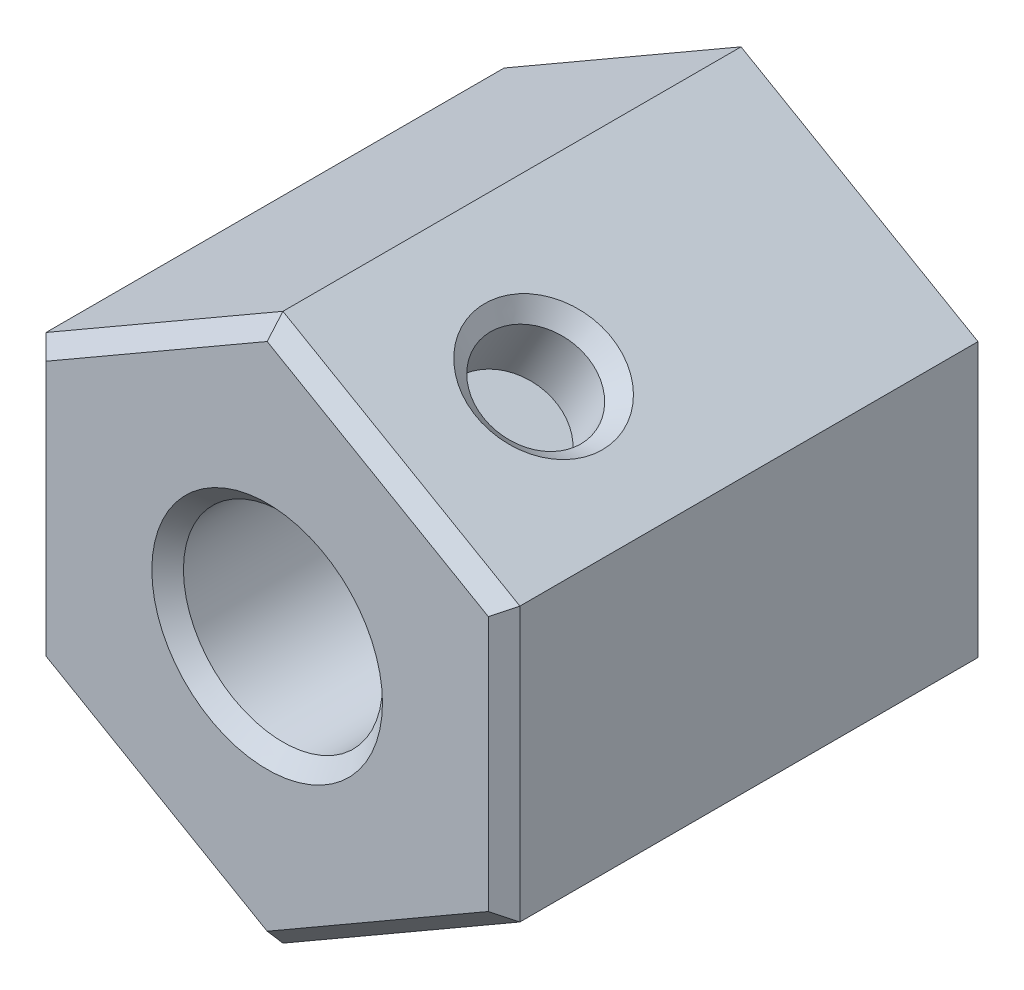
SolidWorks part; units mm, degrees
ref_plane "Front" through (0, 0, 0) normal (0, 0, 1) x (1, 0, 0)
ref_plane "Top" through (0, 0, 0) normal (0, 1, 0) x (1, 0, 0)
ref_plane "Right" through (0, 0, 0) normal (1, 0, 0) x (0, 0, -1)
sketch "Sketch1" plane through (0, 0, 0) normal (0, 0, 1) x (1, 0, 0)
  line L1 (0, 8.6603) -> (-7.5, 4.3301)
  line L2 (-7.5, 4.3301) -> (-7.5, -4.3301)
  line L3 (-7.5, -4.3301) -> (0, -8.6603)
  line L4 (0, -8.6603) -> (7.5, -4.3301)
  line L5 (7.5, -4.3301) -> (7.5, 4.3301)
  line L6 (7.5, 4.3301) -> (0, 8.6603)
  circle A0 centre (0, 0) radius 7.5 construction
  dimension "D1" = 15
extrude "Boss-Extrude1" add sketch "Sketch1" along normal blind 15
sketch "Sketch2" plane through (0, 0, 15) normal (0, 0, 1) x (1, 0, 0)
  circle A0 centre (0, 0) radius 3.15
  dimension "D1" = 6.3
extrude "Cut-Extrude1" cut sketch "Sketch2" against normal blind 15
sketch "Sketch3" plane through (0, 0, 0) normal (0, 0, -1) x (-1, 0, 0)
  line L0 (-7.5, 4.3301) -> (0, 8.6603) construction
  line L1 (0, 5.889) -> (-5.1, 2.9445)
  line L2 (-5.1, 2.9445) -> (-5.1, -2.9445)
  line L3 (-5.1, -2.9445) -> (0, -5.889)
  line L4 (0, -5.889) -> (5.1, -2.9445)
  line L5 (5.1, -2.9445) -> (5.1, 2.9445)
  line L6 (5.1, 2.9445) -> (0, 5.889)
  circle A0 centre (0, 0) radius 5.1 construction
  dimension "D1" = 10.2
extrude "Cut-Extrude2" cut sketch "Sketch3" against normal blind 2.5
sketch "Sketch4" plane through (3.75, 6.4952, 0) normal (0.5, 0.866, 0) x (0.866, -0.5, 0)
  line L0 (4.3301, 0) -> (-4.3301, 0) construction
  circle A0 centre (0, -10) radius 1.65
  point P5 (0, 0)
  dimension "D1" = 3.3
  dimension "D2" = 10
extrude "Cut-Extrude3" cut sketch "Sketch4" against normal blind 2.5
ref_axis "Axis1" through (0, 0, 2.5) along (0, 0, 1)
pattern_circular "CirPattern1" count 3 over 360 about axis through (0, 0, 15) along (0, 0, 1) of "Cut-Extrude3"
chamfer "Chamfer1" distance 0.5 angle 45 7 edges at (7.5, 0, 15) (3.75, -6.4952, 15) (-3.75, -6.4952, 15) (-7.5, 0, 15) (-3.75, 6.4952, 15) (3.75, 6.4952, 15) (3.15, 0, 15)
chamfer "Chamfer2" distance 0.5 angle 45 3 edges at (-7.5, -1.65, 10) (5.1789, -5.6702, 10) (2.3211, 7.3202, 10)
chamfer "Chamfer3" distance 0.5 angle 45 1 edges at (-3.15, 0, 2.5)
